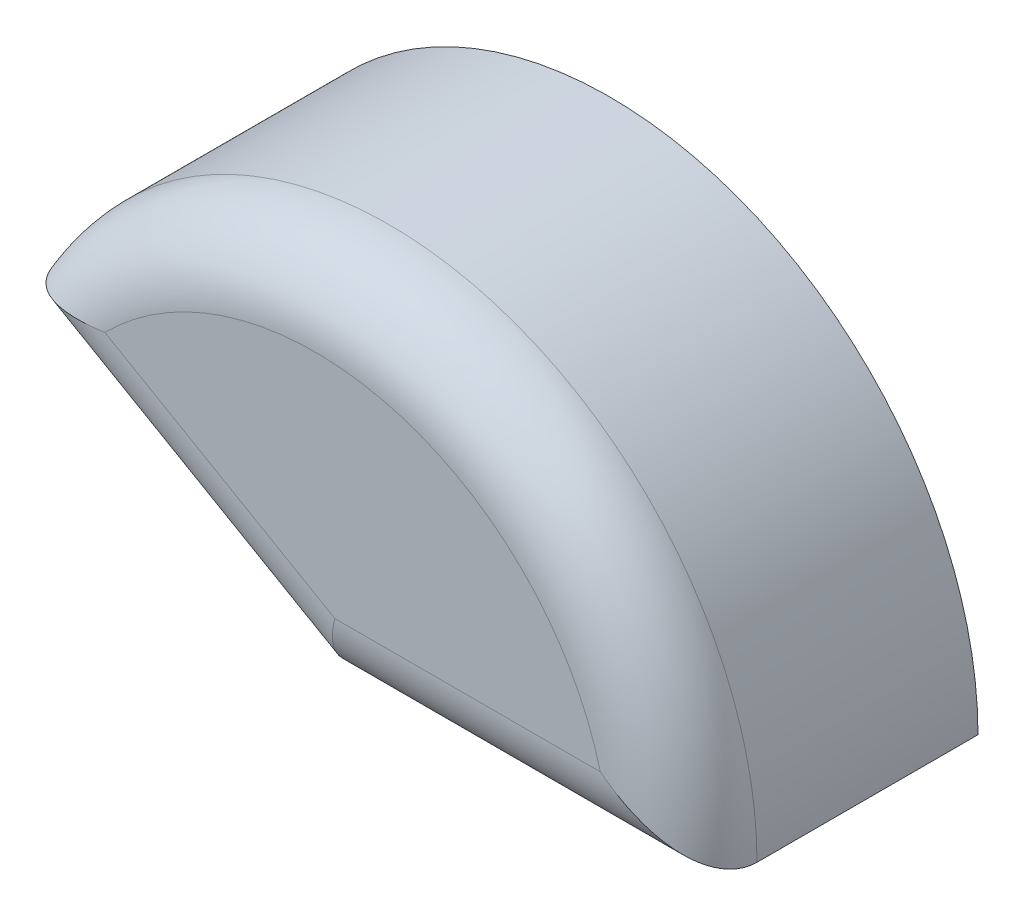
SolidWorks part; units mm, degrees
ref_plane "Front Plane" through (0, 0, 0) normal (0, 0, 1) x (1, 0, 0)
ref_plane "Top Plane" through (0, 0, 0) normal (0, 1, 0) x (1, 0, 0)
ref_plane "Right Plane" through (0, 0, 0) normal (1, 0, 0) x (0, 0, -1)
sketch "Sketch1" plane through (0, 0, 0) normal (0, 0, 1) x (1, 0, 0)
  line L0 (-21.6506, 12.5) -> (0, 0)
  line L1 (0, 0) -> (25, 0)
  arc A0 (25, 0) -> (-21.6506, 12.5) centre (0, 0) ccw
  dimension "D1" = 150
  dimension "D2" = 25
extrude "Boss-Extrude1" add sketch "Sketch1" along normal blind 20
fillet "Fillet1" radius 5 3 edges at (-10.8253, 6.25, 20) (6.4705, 24.1481, 20) (12.5, 0, 20)
equation "\"angle\"=150"
equation "\"thicknes\"=20"
equation "\"diameter\"=25"
equation "\"D1@Sketch1\"= \"angle\""
equation "\"D2@Sketch1\"= \"diameter\""
equation "\"D1@Boss-Extrude1\"= \"thicknes\""
